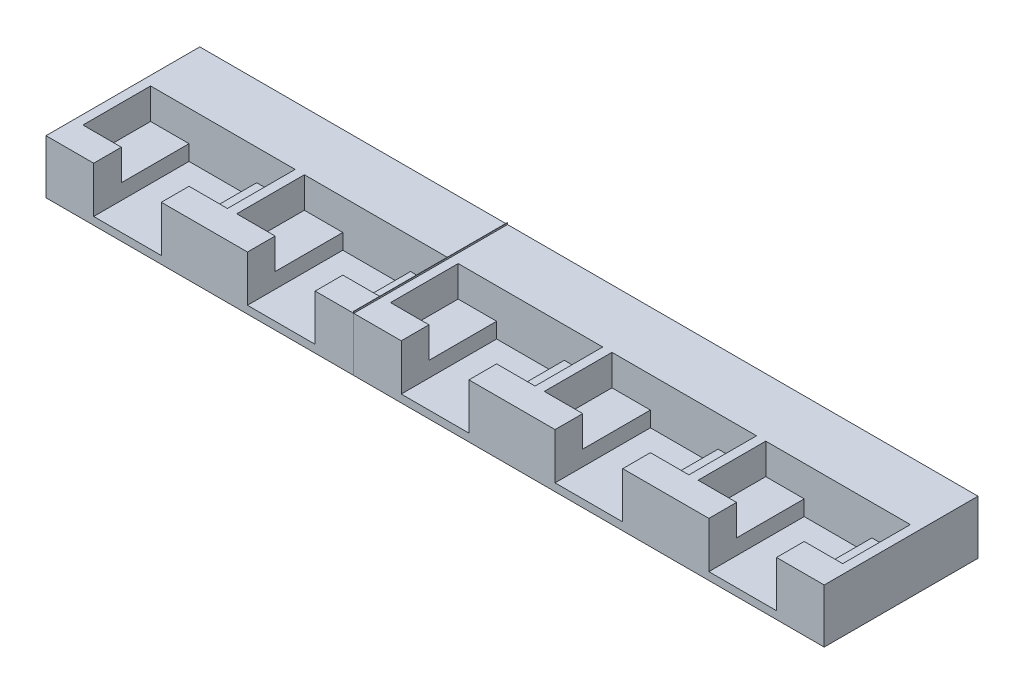
SolidWorks part; units mm, degrees
ref_plane "Front Plane" through (0, 0, 0) normal (0, 0, 1) x (1, 0, 0)
ref_plane "Top Plane" through (0, 0, 0) normal (0, 1, 0) x (1, 0, 0)
ref_plane "Right Plane" through (0, 0, 0) normal (1, 0, 0) x (0, 0, -1)
sketch "Sketch1" plane through (0, 0, 0) normal (0, 1, 0) x (1, 0, 0)
  line L1 (0, 15) -> (253, 15)
  line L2 (0, 15) -> (0, -35)
  line L3 (0, -35) -> (253, -35)
  line L4 (253, 15) -> (253, -35)
  line L5 (0, -35) -> (65.5768, -35)
  line L6 (0, -35) -> (0, -21.0008)
extrude "Boss-Extrude1" add sketch "Sketch1" along normal blind 17.5 contours L1 L4 L3 L2
sketch "Sketch2" plane through (0, 17.5, 0) normal (0, 1, 0) x (1, 0, 0)
  line L1 (3, -4) -> (50, -4)
  line L2 (3, -4) -> (3, -26)
  line L3 (3, -26) -> (50, -26)
  line L4 (50, -4) -> (50, -26)
extrude "Cut-Extrude1" cut sketch "Sketch2" against normal blind 10
sketch "Sketch4" plane through (0, 17.5, 0) normal (0, 1, 0) x (1, 0, 0)
  line L1 (15.5, -4) -> (37.5, -4)
  line L2 (15.5, -4) -> (15.5, -35)
  line L3 (15.5, -35) -> (37.5, -35)
  line L4 (37.5, -4) -> (37.5, -35)
extrude "Cut-Extrude2" cut sketch "Sketch4" against normal blind 15
ref_plane "Plane1" through (51.5, 0, 0) normal (-1, 0, 0) x (0, 0, 1)
mirror "Mirror1" about plane through (51.5, 0, 0) normal (-1, 0, 0) of "Cut-Extrude2", "Cut-Extrude1"
ref_plane "Plane2" through (101.5, 0, 0) normal (-1, 0, 0) x (0, 0, 1)
mirror "Mirror2" about plane through (101.5, 0, 0) normal (-1, 0, 0) of "Mirror1"
ref_plane "Plane4" through (126.5, 0, 0) normal (-1, 0, 0) x (0, 0, 1)
mirror "Mirror3" about plane through (126.5, 0, 0) normal (-1, 0, 0) of "Cut-Extrude2", "Cut-Extrude1"
ref_plane "Plane5" through (100, 0, 0) normal (-1, 0, 0) x (0, 0, 1)
sketch "Sketch5" plane through (100, 0, 0) normal (-1, 0, 0) x (0, 0, 1)
  line L1 (-15, 18) -> (35, 18)
  line L2 (-15, 18) -> (-15, 0)
  line L3 (-15, 0) -> (35, 0)
  line L4 (35, 18) -> (35, 0)
  point P4 (-15, 17.5)
  point P5 (-15.4781, 16.3193)
  point P6 (0, 0)
  point P7 (-15, 0)
  point P8 (0, 0)
  point P9 (35.0441, 16.6755)
  point P10 (0, 0)
  point P11 (0, 0)
  point P12 (-15, 17.5)
  point P13 (0, 0)
  point P15 (0, 0)
  point P16 (0, 0)
  point P17 (0, 0)
  point P18 (0, 0)
extrude "Boss-Extrude2" add sketch "Sketch5" along normal mid plane 0.1
split "Split1" bodies to split 107 resulting bodies 108 109 split by face at (100.05, 17.75, 10)
